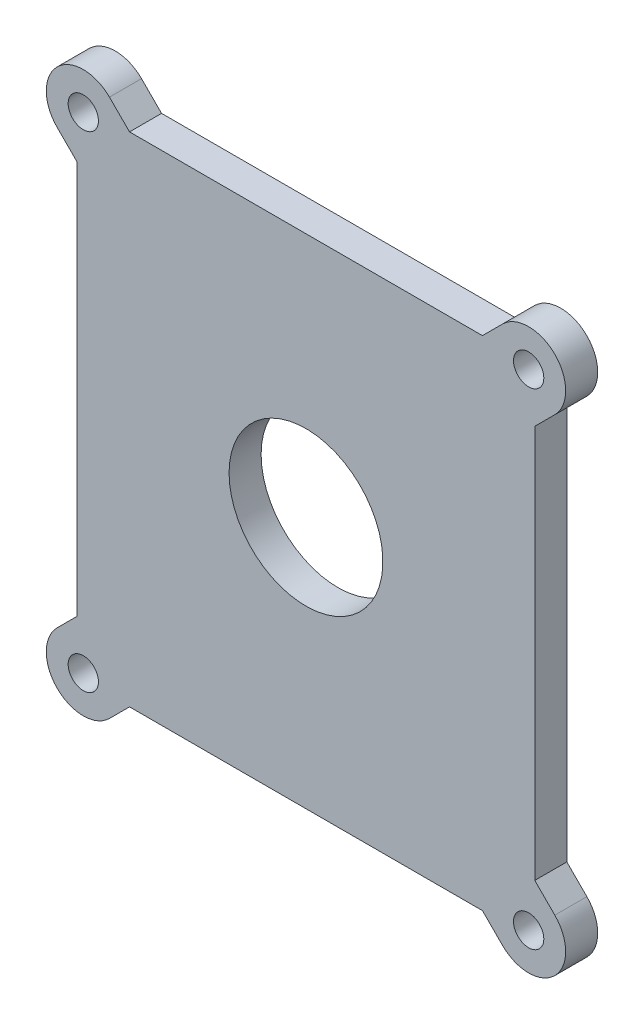
SolidWorks part; units mm, degrees
material "Acrylic (Medium-high impact)"
ref_plane "X-Y Datum" through (0, 0, 0) normal (0, 0, 1) x (1, 0, 0)
ref_plane "X-Z Datum" through (0, 0, 0) normal (0, 1, 0) x (1, 0, 0)
ref_plane "Y-Z Datum" through (0, 0, 0) normal (1, 0, 0) x (0, 0, -1)
sketch "Sketch4" plane through (0, 0, -16.1083) normal (0, 0, 1) x (1, 0, 0)
  line L12 (25.9503, 36.9951) -> (-26.4934, 36.9951)
  line L13 (-26.4934, 36.9951) -> (-29.4738, 39.9756)
  line L14 (-37.252, 32.1974) -> (-34.2715, 29.2169)
  line L15 (-34.2715, 29.2169) -> (-34.2715, -29.2267)
  line L16 (-34.2715, -29.2267) -> (-37.252, -32.2072)
  line L17 (-29.4738, -39.9854) -> (-26.4934, -37.0049)
  line L18 (-26.4934, -37.0049) -> (25.9503, -37.0049)
  line L19 (25.9503, -37.0049) -> (28.9307, -39.9854)
  line L20 (36.7089, -32.2072) -> (33.7285, -29.2267)
  line L21 (33.7285, -29.2267) -> (33.7285, 29.2169)
  line L22 (33.7285, 29.2169) -> (36.7089, 32.1974)
  line L23 (28.9307, 39.9756) -> (25.9503, 36.9951)
  line L24 (25.9503, 36.9951) -> (-26.4934, 36.9951)
  line L25 (-26.4934, 36.9951) -> (-29.4738, 39.9756)
  line L26 (-37.252, 32.1974) -> (-34.2715, 29.2169)
  line L27 (-34.2715, 29.2169) -> (-34.2715, -29.2267)
  line L28 (-34.2715, -29.2267) -> (-37.252, -32.2072)
  line L29 (-29.4738, -39.9854) -> (-26.4934, -37.0049)
  line L30 (-26.4934, -37.0049) -> (25.9503, -37.0049)
  line L31 (25.9503, -37.0049) -> (28.9307, -39.9854)
  line L32 (36.7089, -32.2072) -> (33.7285, -29.2267)
  line L33 (33.7285, -29.2267) -> (33.7285, 29.2169)
  line L34 (33.7285, 29.2169) -> (36.7089, 32.1974)
  line L35 (28.9307, 39.9756) -> (25.9503, 36.9951)
  circle A0 centre (-0.2715, 0.4951) radius 11.43
  arc A4 (-29.4738, 39.9756) -> (-37.252, 32.1974) centre (-33.3629, 36.0865) ccw
  arc A5 (-37.252, -32.2072) -> (-29.4738, -39.9854) centre (-33.3629, -36.0963) ccw
  arc A6 (28.9307, -39.9854) -> (36.7089, -32.2072) centre (32.8198, -36.0963) ccw
  arc A7 (36.7089, 32.1974) -> (28.9307, 39.9756) centre (32.8198, 36.0865) ccw
  arc A8 (-29.4738, 39.9756) -> (-37.252, 32.1974) centre (-33.3629, 36.0865) ccw
  arc A9 (-37.252, -32.2072) -> (-29.4738, -39.9854) centre (-33.3629, -36.0963) ccw
  arc A10 (28.9307, -39.9854) -> (36.7089, -32.2072) centre (32.8198, -36.0963) ccw
  arc A11 (36.7089, 32.1974) -> (28.9307, 39.9756) centre (32.8198, 36.0865) ccw
  point P14 (-0.2715, 0.4951)
  dimension "D2" = 22.86
  dimension "D1" = 0
extrude "Boss-Extrude1" add sketch "Sketch4" along normal blind 4.7625
hole_wizard "M4 Clearance Hole2" positions "Sketch5" profile "Sketch6" hole size "M4" standard "ANSI Metric" end condition through all
sketch "Sketch5" plane through (0, 0, -11.3458) normal (0, 0, 1) x (1, 0, 0)
  point P0 (-33.3629, 36.0865)
  point P3 (32.8198, 36.0865)
  point P6 (32.8198, -36.0963)
  point P9 (-33.3629, -36.0963)
sketch "Sketch6" plane through (-33.3629, 36.0865, -11.3458) normal (1, 0, 0) x (0, -1, 0)
  line L0 (0, 0) -> (0, 4.7625)
  line L1 (0, 4.7625) -> (2.25, 4.7625)
  line L2 (2.25, 4.7625) -> (2.25, 0)
  line L5 (2.25, 0) -> (0, 0)
  line L11 (0, -6.35) -> (0, 107.95) construction
  dimension "Thru Hole Dia." = 4.5
  dimension "Thru Hole Depth" = 4.7625
